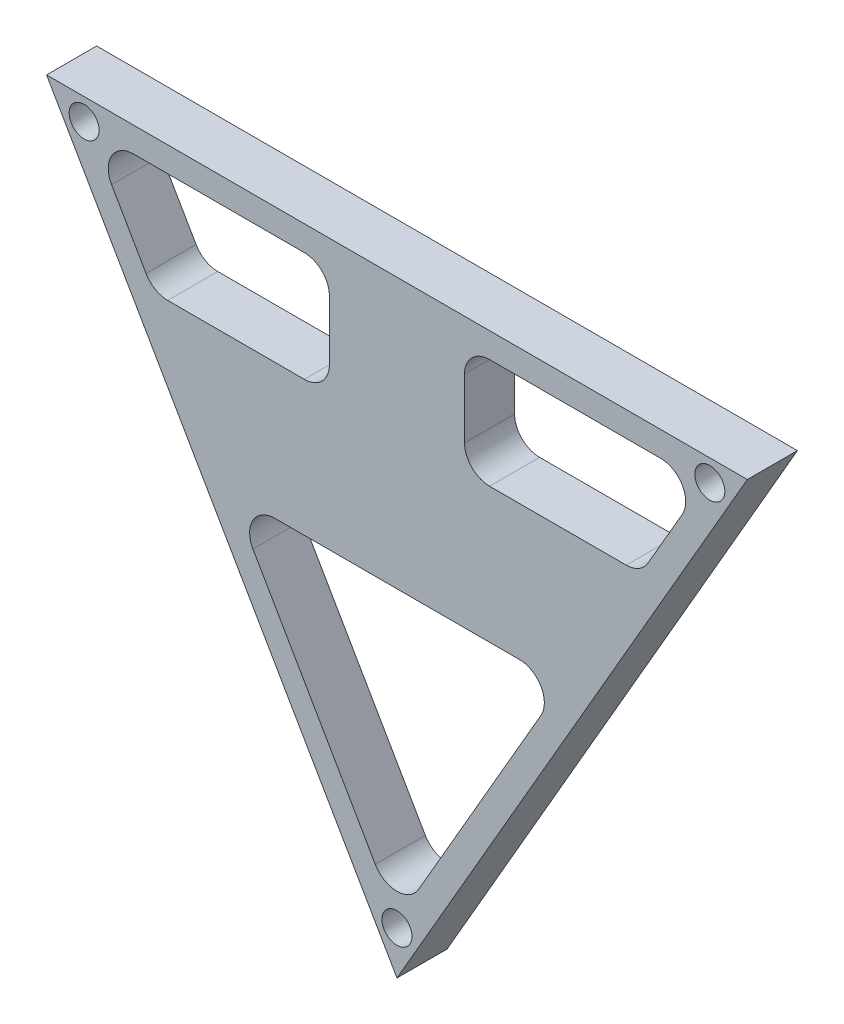
SolidWorks part; units mm, degrees
material "ABS"
ref_plane "Front Plane" through (0, 0, 0) normal (0, 0, 1) x (1, 0, 0)
ref_plane "Top Plane" through (0, 0, 0) normal (0, 1, 0) x (1, 0, 0)
ref_plane "Right Plane" through (0, 0, 0) normal (1, 0, 0) x (0, 0, -1)
sketch "Sketch1" plane through (0, 0, 0) normal (0, 0, 1) x (1, 0, 0)
  line L1 (0, -80.829) -> (70, 40.4145)
  line L2 (70, 40.4145) -> (-70, 40.4145)
  line L3 (-70, 40.4145) -> (0, -80.829)
  circle A0 centre (0, 0) radius 40.4145 construction
  dimension "D1" = 140
extrude "Boss-Extrude1" add sketch "Sketch1" along normal blind 10
sketch "Sketch2" plane through (0, 0, 0) normal (0, 0, -1) x (-1, 0, 0)
  line L1 (-11.5, -11.5) -> (11.5, -11.5)
  line L2 (-11.5, -11.5) -> (-11.5, 11.5)
  line L3 (-11.5, 11.5) -> (11.5, 11.5)
  line L4 (11.5, -11.5) -> (11.5, 11.5)
  line L5 (-11.5, -11.5) -> (11.5, 11.5) construction
  line L6 (-11.5, 11.5) -> (11.5, -11.5) construction
  point P0 (0, 0)
  dimension "D1" = 23
  dimension "D2" = 23
extrude "Cut-Extrude1" cut sketch "Sketch2" against normal blind 3
sketch "Sketch3" plane through (0, 0, 3) normal (0, 0, -1) x (-1, 0, 0)
  line L0 (11.5, 11.5) -> (-11.5, 11.5) construction
  line L1 (-11.5, 11.5) -> (-11.5, -11.5) construction
  line L3 (-8, -8) -> (8, -8) construction
  line L4 (-8, -8) -> (-8, 8) construction
  line L5 (-8, 8) -> (8, 8) construction
  line L6 (8, -8) -> (8, 8) construction
  line L7 (-8, -8) -> (8, 8) construction
  line L8 (-8, 8) -> (8, -8) construction
  circle A0 centre (-8, 8) radius 1.5
  circle A1 centre (8, 8) radius 1.5
  circle A2 centre (8, -8) radius 1.5
  circle A3 centre (-8, -8) radius 1.5
  point P9 (0, 0)
  dimension "D1" = 3
  dimension "D2" = 3.5
  dimension "D3" = 3.5
extrude "Cut-Extrude2" cut sketch "Sketch3" against normal through all both and the other way through all
sketch "Sketch4" plane through (0, 0, 0) normal (0, 0, -1) x (-1, 0, 0)
  line L1 (10.13, 17.22) -> (-10.13, 17.22)
  line L2 (10.13, 17.22) -> (10.13, 32.78)
  line L3 (10.13, 32.78) -> (-10.13, 32.78)
  line L4 (-10.13, 17.22) -> (-10.13, 32.78)
  line L5 (10.13, 17.22) -> (-10.13, 32.78) construction
  line L6 (10.13, 32.78) -> (-10.13, 17.22) construction
  point P0 (0, 25)
  dimension "D1" = 20.26
  dimension "D2" = 15.56
  dimension "D3" = 25
extrude "Cut-Extrude3" cut sketch "Sketch4" against normal blind 3 and the other way through all
sketch "Sketch5" plane through (0, 0, 3) normal (0, 0, -1) x (-1, 0, 0)
  line L0 (-7.53, 30.14) -> (7.53, 30.14) construction
  line L1 (10.13, 32.78) -> (-10.13, 32.78) construction
  circle A0 centre (-7.53, 30.14) radius 1.425
  circle A1 centre (7.53, 30.14) radius 1.425
  point P4 (0, 30.14)
  dimension "D2" = 2.85
  dimension "D1" = 15.06
  dimension "D3" = 2.64
extrude "Cut-Extrude4" cut sketch "Sketch5" against normal through all both and the other way through all
sketch "Sketch6" plane through (0, 0, 0) normal (0, 0, -1) x (-1, 0, 0)
  line L4 (11.5, -11.5) -> (11.5, 11.5) construction
  line L5 (11.5, 11.5) -> (-11.5, 11.5) construction
  line L6 (-11.5, 11.5) -> (-11.5, -11.5) construction
  line L7 (-11.5, -11.5) -> (11.5, -11.5) construction
  line L12 (11.5, -11.5) -> (11.5, 11.5)
  line L13 (11.5, 11.5) -> (-11.5, 11.5)
  line L14 (-11.5, 11.5) -> (-11.5, -11.5)
  line L15 (-11.5, -11.5) -> (11.5, -11.5)
  line L16 (-61.3397, 35.4145) -> (-48.6874, 13.5)
  line L17 (0, -70.829) -> (33.0989, -13.5)
  line L18 (61.3397, 35.4145) -> (13.5, 35.4145)
  line L19 (0, -80.829) -> (70, 40.4145)
  line L20 (70, 40.4145) -> (-70, 40.4145)
  line L21 (-70, 40.4145) -> (0, -80.829)
  line L22 (0, -80.829) -> (70, 40.4145)
  line L23 (70, 40.4145) -> (-70, 40.4145)
  line L24 (-70, 40.4145) -> (0, -80.829)
  line L28 (-13.5, -13.5) -> (13.5, -13.5)
  line L33 (13.5, -13.5) -> (33.0989, -13.5)
  line L34 (13.5, 13.5) -> (48.6874, 13.5)
  line L35 (-13.5, -13.5) -> (-33.0989, -13.5)
  line L36 (-13.5, 13.5) -> (-48.6874, 13.5)
  line L37 (-13.5, 13.5) -> (-13.5, 35.4145)
  line L38 (13.5, 13.5) -> (13.5, 35.4145)
  line L39 (-33.0989, -13.5) -> (0, -70.829)
  line L40 (-61.3397, 35.4145) -> (0, -70.829) construction
  line L41 (48.6874, 13.5) -> (61.3397, 35.4145)
  line L42 (0, -70.829) -> (61.3397, 35.4145) construction
  line L43 (-13.5, 35.4145) -> (-61.3397, 35.4145)
  line L44 (61.3397, 35.4145) -> (-61.3397, 35.4145) construction
  line L47 (13.5, -13.5) -> (13.5, 13.5) construction
  line L48 (13.5, 13.5) -> (-13.5, 13.5) construction
  line L49 (-13.5, 13.5) -> (-13.5, -13.5) construction
  dimension "D1" = 0
  dimension "D2" = 5
  dimension "D3" = 2
extrude "Cut-Extrude6" cut sketch "Sketch6" against normal through all both and the other way through all contours L37 L43 L16 L36 | L34 L41 L18 L38 | L35 L39 L17 L33 L28 region at (34.4175, 25.0138, 0) region at (0, -32.6097, 0) region at (-34.4175, 25.0138, 0)
sketch "Sketch7" plane through (0, 0, 0) normal (0, 0, -1) x (-1, 0, 0)
  line L0 (13.5, 11.5) -> (13.5, -11.5)
  line L1 (13.5, -11.5) -> (34.2536, -11.5)
  line L2 (34.2536, -11.5) -> (47.5327, 11.5)
  line L3 (47.5327, 11.5) -> (13.5, 11.5)
  line L4 (11.5, 11.5) -> (-11.5, 11.5) construction
  line L5 (-11.5, -11.5) -> (11.5, -11.5) construction
  line L6 (13.5, 35.4145) -> (13.5, 13.5) construction
  line L7 (33.0989, -13.5) -> (0, -70.829) construction
extrude "Cut-Extrude7" [suppressed] cut sketch "Sketch7" against normal through all both and the other way through all
mirror "Mirror1" [suppressed] about plane through (0, 0, 0) normal (1, 0, 0)
fillet "Fillet1" radius 5 11 edges at (0, -70.829, 5) (-33.0989, -13.5, 5) (33.0989, -13.5, 5) (61.3397, 35.4145, 5) (48.6874, 13.5, 5) (-48.6874, 13.5, 5) (-61.3397, 35.4145, 5) (-13.5, 35.4145, 5) (13.5, 35.4145, 5) (13.5, 13.5, 5) (-13.5, 13.5, 5)
sketch "Sketch8" plane through (0, 17.22, 0) normal (0, 1, 0) x (1, 0, 0)
  line L4 (10.13, 0) -> (-10.13, 0)
  line L5 (-10.13, 0) -> (-10.13, -3)
  line L6 (-10.13, -3) -> (10.13, -3)
  line L7 (10.13, -3) -> (10.13, 0)
  line L8 (10.13, 0) -> (-10.13, 0)
  line L9 (-10.13, 0) -> (-10.13, -3)
  line L10 (-10.13, -3) -> (10.13, -3)
  line L11 (10.13, -3) -> (10.13, 0)
  dimension "D1" = 0
extrude "Cut-Extrude8" cut sketch "Sketch8" against normal up to surface (28.72 mm away) up to face at (0, -11.5, 1.5)
chamfer "Chamfer1" distance 1.37 angle 45 2 edges at (10.13, 11.5, 1.5) (-10.13, 11.5, 1.5)
sketch "Sketch9" plane through (0, 0, 0) normal (0, 0, -1) x (-1, 0, 0)
  line L1 (-62.5, 36.0844) -> (0, -72.1688) construction
  line L2 (0, -72.1688) -> (62.5, 36.0844) construction
  line L3 (62.5, 36.0844) -> (-62.5, 36.0844) construction
  circle A0 centre (0, 0) radius 36.0844 construction
  circle A1 centre (-62.5, 36.0844) radius 1.65
  circle A2 centre (62.5, 36.0844) radius 1.65
  circle A3 centre (0, -72.1688) radius 1.65
  dimension "D2" = 3.3
  dimension "D3" = 3.3
  dimension "D4" = 3.3
  dimension "D1" = 125
extrude "Cut-Extrude9" cut sketch "Sketch9" against normal through all
sketch "Sketch10" plane through (0, 0, 10) normal (0, 0, -1) x (-1, 0, 0)
  circle A0 centre (-62.5, 36.0844) radius 3
  circle A1 centre (62.5, 36.0844) radius 3
  circle A2 centre (0, -72.1688) radius 3
  circle A4 centre (0, -72.1688) radius 1.65 construction
  dimension "D1" = 6
extrude "Cut-Extrude10" cut sketch "Sketch10" along normal offset from surface (5 mm away) 5 up to face at (-64.15, 36.0844, 0)
sketch "Sketch11" plane through (0, 0, 10) normal (0, 0, 1) x (1, 0, 0)
  line L0 (-8, 4.82) -> (-5.246, 6.41)
  line L1 (-8, 11.18) -> (-10.754, 9.59)
  line L2 (-10.754, 9.59) -> (-10.754, 6.41)
  line L3 (-10.754, 6.41) -> (-8, 4.82)
  line L4 (-5.246, 6.41) -> (-5.246, 9.59)
  line L5 (-5.246, 9.59) -> (-8, 11.18)
  line L7 (8, 4.82) -> (10.754, 6.41)
  line L8 (10.754, 6.41) -> (10.754, 9.59)
  line L9 (10.754, 9.59) -> (8, 11.18)
  line L10 (8, 11.18) -> (5.246, 9.59)
  line L11 (5.246, 9.59) -> (5.246, 6.41)
  line L12 (5.246, 6.41) -> (8, 4.82)
  line L13 (5.246, -6.41) -> (5.246, -9.59)
  line L14 (5.246, -9.59) -> (8, -11.18)
  line L15 (8, -11.18) -> (10.754, -9.59)
  line L16 (10.754, -9.59) -> (10.754, -6.41)
  line L17 (10.754, -6.41) -> (8, -4.82)
  line L18 (8, -4.82) -> (5.246, -6.41)
  line L19 (-8, -4.82) -> (-10.754, -6.41)
  line L20 (-10.754, -6.41) -> (-10.754, -9.59)
  line L21 (-10.754, -9.59) -> (-8, -11.18)
  line L22 (-8, -11.18) -> (-5.246, -9.59)
  line L23 (-5.246, -9.59) -> (-5.246, -6.41)
  line L24 (-5.246, -6.41) -> (-8, -4.82)
  line L25 (-8, 8) -> (8, 8) construction
  line L26 (-8, 8) -> (-8, -8) construction
  line L27 (-8, -8) -> (8, -8) construction
  line L28 (8, 8) -> (8, -8) construction
  circle A0 centre (-8, 8) radius 2.754 construction
  circle A1 centre (8, 8) radius 2.754 construction
  circle A2 centre (8, -8) radius 2.754 construction
  circle A3 centre (-8, -8) radius 2.754 construction
  dimension "D1" = 3.18
extrude "Cut-Extrude11" [suppressed] cut sketch "Sketch11" against normal blind 3
sketch "Sketch12" plane through (0, 0, 3) normal (0, 0, -1) x (-1, 0, 0)
  circle A0 centre (-8, 8) radius 1.75
  circle A1 centre (8, 8) radius 1.75
  circle A2 centre (8, -8) radius 1.75
  circle A3 centre (-8, -8) radius 1.75
  circle A6 centre (-7.53, 30.14) radius 1.425
  circle A7 centre (7.53, 30.14) radius 1.425
  circle A8 centre (-7.53, 30.14) radius 1.425 construction
  dimension "D1" = 3.5
extrude "Boss-Extrude2" add sketch "Sketch12" along normal blind 2.5 and the other way through all
chamfer "Chamfer2" distance 2 angle 45 3 edges at (64.15, 36.0844, 5) (-60.85, 36.0844, 5) (1.65, -72.1688, 5)
chamfer "Chamfer3" distance 1.25 angle 45 6 edges at (6.25, -8, 0.5) (-9.75, -8, 0.5) (-9.75, 8, 0.5) (6.25, 8, 0.5) (6.105, 30.14, 0.5) (-8.955, 30.14, 0.5)
